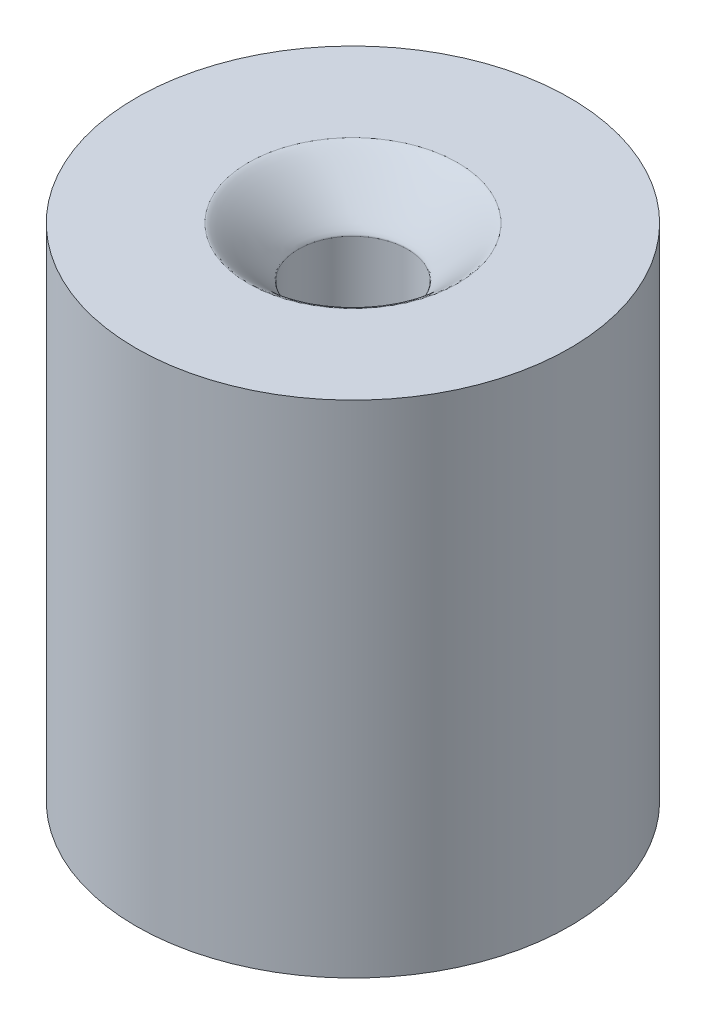
SolidWorks part; units mm, degrees
ref_plane "Front Plane" through (0, 0, 0) normal (0, 0, 1) x (1, 0, 0)
ref_plane "Top Plane" through (0, 0, 0) normal (0, 1, 0) x (1, 0, 0)
ref_plane "Right Plane" through (0, 0, 0) normal (1, 0, 0) x (0, 0, -1)
sketch "Sketch1" plane through (0, 0, 0) normal (0, 1, 0) x (1, 0, 0)
  circle A0 centre (0, 0) radius 6.5
  dimension "D1" = 13
extrude "Boss-Extrude1" add sketch "Sketch1" along normal blind 15
sketch "Sketch2" plane through (0, 15, 0) normal (0, 1, 0) x (1, 0, 0)
  line L0 (0, 6.5) -> (0, -6.5) construction
  circle A0 centre (0, 0) radius 6.5 construction
  circle A1 centre (0, 0) radius 1.6383
  dimension "D1" = 3.2766
extrude "Cut-Extrude1" cut sketch "Sketch2" against normal through all both and the other way through all
fillet "Fillet1" radius 1.5 1 edges at (0, 15, 1.6383) conic radius 10
